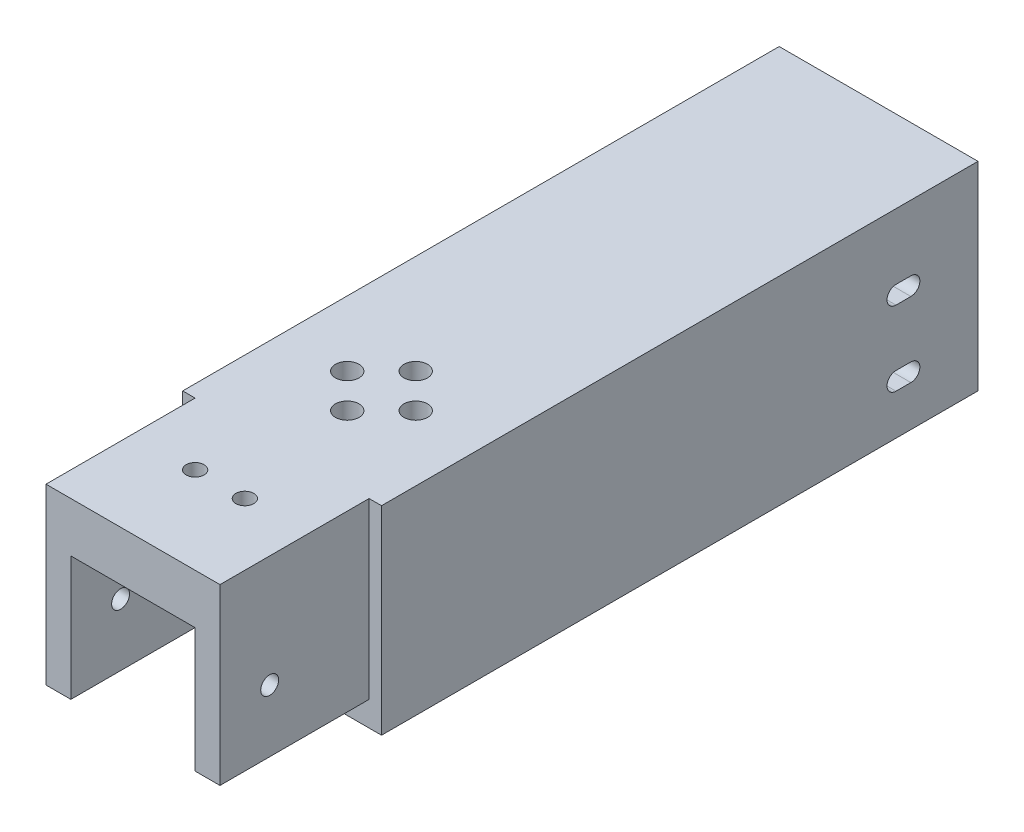
SolidWorks part; units mm, degrees
ref_plane "Front Plane" through (0, 0, 0) normal (0, 0, 1) x (1, 0, 0)
ref_plane "Top Plane" through (0, 0, 0) normal (0, 1, 0) x (1, 0, 0)
ref_plane "Right Plane" through (0, 0, 0) normal (1, 0, 0) x (0, 0, -1)
sketch "Sketch1" plane through (0, 0, 0) normal (0, 1, 0) x (1, 0, 0)
  line L9 (-20, -20) -> (20, -20)
  line L10 (-20, -20) -> (-20, 20)
  line L11 (-20, 20) -> (20, 20)
  line L12 (20, -20) -> (20, 20)
  line L13 (-20, -20) -> (20, 20) construction
  line L14 (-20, 20) -> (20, -20) construction
  circle A0 centre (6.88, 0) radius 2.375
  circle A1 centre (-0.0097, -6.8897) radius 2.375
  circle A2 centre (-6.8993, 0) radius 2.375
  circle A3 centre (-0.0097, 6.8897) radius 2.375
  point P2 (0, 0)
  point P12 (-0.0097, 0)
  dimension "D2" = 4.75
  dimension "D3" = 4
  dimension "D4" = 40
  dimension "D1" = 6.88
  dimension "D5" = 40
extrude "Boss-Extrude1" add sketch "Sketch1" along normal blind 40
sketch "Sketch3" plane through (0, 0, 20) normal (0, 0, 1) x (1, 0, 0)
  line L0 (-20, 0) -> (35335.3391, 35355.3391) construction
  line L1 (-20, 40) -> (35335.3391, -35315.3391) construction
  line L2 (-20, 40) -> (-20, 0) construction
  line L5 (-20, 0) -> (20, 0) construction
  line L6 (20, 40) -> (20, 0) construction
  circle A2 centre (0, 13) radius 3
  circle A3 centre (-7, 20) radius 3
  circle A4 centre (7, 20) radius 3
  point P10 (0, 20)
  dimension "D2" = 6
  dimension "D3" = 6
  dimension "D1" = 6
  dimension "D4" = 13
  dimension "D5" = 13
  dimension "D6" = 13
sketch "Sketch4" plane through (-20, 0, 0) normal (-1, 0, 0) x (0, 0, 1)
  line L0 (-20, 35) -> (-20, 0)
  line L1 (-20, 40) -> (-20, 0) construction
  line L2 (-20, 0) -> (15, 0)
  arc A0 (-20, 35) -> (15, 0) centre (-20, 0) cw
extrude "Cut-Extrude1" cut sketch "Sketch4" along normal through all both and the other way through all
sketch "Sketch6" plane through (0, 0, 0) normal (0, -1, 0) x (1, 0, 0)
  line L0 (20, -20) -> (-20, -20) construction
  line L2 (-15, 15) -> (-15, -20)
  line L3 (-15, -20) -> (15, -20)
  line L4 (15, 15) -> (15, -20)
  line L5 (-11.25, 15) -> (15, -20) construction
  line L6 (-15, -20) -> (11.25, 15) construction
  line L7 (-20, 15) -> (-20, -20) construction
  line L8 (-15, 15) -> (15, 15)
  point P0 (0, 0)
  dimension "D1" = 5
extrude "Cut-Extrude2" cut sketch "Sketch6" against normal blind 35 and the other way through all
extrude "Cut-Extrude3" cut sketch "Sketch3" against normal through all
sketch "Sketch7" plane through (0, 0, 20) normal (0, 0, 1) x (1, 0, 0)
  line L1 (-12.5, 30) -> (12.5, 30) construction
  line L2 (-12.5, 30) -> (-12.5, 5) construction
  line L3 (-12.5, 5) -> (12.5, 5) construction
  line L4 (12.5, 30) -> (12.5, 5) construction
  line L5 (-12.5, 30) -> (12.5, 5) construction
  line L6 (-12.5, 5) -> (12.5, 30) construction
  line L7 (-17.5, 40) -> (17.5, 40)
  line L9 (-12.5, 30) -> (12.5, 30)
  line L12 (-17.5, 23.7908) -> (-17.5, 40)
  line L14 (-12.5, 30) -> (-12.5, 5)
  line L15 (-12.5, 5) -> (-17.5, 5)
  line L16 (-17.5, 23.7908) -> (-17.5, 5)
  line L17 (12.5, 5) -> (17.5, 5)
  line L18 (12.5, 5) -> (12.5, 30)
  line L21 (17.5, 40) -> (17.5, 5)
  line L22 (-20, 40) -> (20, 40) construction
  circle A0 centre (-7, 20) radius 3 construction
  point P0 (0, 17.5)
  dimension "D1" = 7
  dimension "D4" = 10
  dimension "D6" = 5
  dimension "D2" = 25
  dimension "D3" = 25
  dimension "D7" = 5
extrude "Boss-Extrude2" add sketch "Sketch7" along normal blind 30
sketch "Sketch8" plane through (0, 40, 0) normal (0, 1, 0) x (1, 0, 0)
  line L0 (0, -1000) -> (0, 49000) construction
  line L2 (17.5, -20) -> (20, -20) construction
  circle A0 centre (5, -32.5) radius 1.8
  circle A1 centre (-5, -32.5) radius 1.8
  dimension "D3" = 3.6
  dimension "D1" = 5
  dimension "D2" = 12.5
extrude "Cut-Extrude4" cut sketch "Sketch8" against normal through all
sketch "Sketch10" plane through (0, 0, -20) normal (0, 0, -1) x (-1, 0, 0)
  line L2 (-20, 40) -> (-20, 0)
  line L3 (-20, 0) -> (-15, 0)
  line L4 (-15, 35) -> (-15, 0)
  line L5 (15, 0) -> (20, 0)
  line L6 (15, 0) -> (15, 35)
  line L8 (20, 0) -> (20, 40)
  line L9 (15, 35) -> (-15, 35)
  line L10 (20, 35) -> (20, 40)
  line L11 (20, 40) -> (-20, 40)
  line L12 (-20, 35) -> (-20, 40)
  line M5 (-20, 40) -> (-20, 35)
  line M6 (-20, 35) -> (-15, 35)
  line M7 (-15, 35) -> (15, 35)
  line M8 (15, 35) -> (20, 35)
  line M9 (20, 35) -> (20, 40)
  line M10 (20, 40) -> (-20, 40)
  dimension "D1" = 5
sketch "Sketch11" plane through (0, 40, 0) normal (0, 1, 0) x (1, 0, 0)
  circle A0 centre (-0.0097, -6.8897) radius 2.375 construction
  circle A1 centre (6.88, 0) radius 2.375 construction
  circle A2 centre (-0.0097, 6.8897) radius 2.375 construction
  circle A3 centre (-6.8993, 0) radius 2.375 construction
  circle A4 centre (-0.0097, -6.8897) radius 2.375
  circle A5 centre (6.88, 0) radius 2.375
  circle A6 centre (-0.0097, 6.8897) radius 2.375
  circle A7 centre (-6.8993, 0) radius 2.375
extrude "Boss-Extrude4" add sketch "Sketch10" along normal blind 80 and the other way up to surface (40 mm away) contours M10 M5 M6 M7 M8 M9 | L5 L8 L6 M8 | L4 L2 L3 M6 region at (0, 37.5, -20) region at (17.5, 17.5, -20) region at (-17.5, 17.5, -20) other way up to face at (10, 20, 20)
extrude "Cut-Extrude5" cut sketch "Sketch11" against normal blind 70
sketch "Sketch13" plane through (-20, 0, 0) normal (-1, 0, 0) x (0, 0, 1)
  line L0 (-86.5, 25) -> (-83.5, 25) construction
  line L1 (-86.5, 26.8) -> (-83.5, 26.8)
  line L2 (-86.5, 23.2) -> (-83.5, 23.2)
  line L3 (-100, 40) -> (20, 40) construction
  line L4 (-100, 0) -> (-100, 40) construction
  line L5 (-1100, 17.5) -> (48900, 17.5) construction
  line L7 (-100, 0) -> (20, 0) construction
  line L8 (-86.5, 10) -> (-83.5, 10) construction
  line L9 (-86.5, 8.2) -> (-83.5, 8.2)
  line L10 (-86.5, 11.8) -> (-83.5, 11.8)
  arc A0 (-86.5, 26.8) -> (-86.5, 23.2) centre (-86.5, 25) ccw
  arc A1 (-83.5, 23.2) -> (-83.5, 26.8) centre (-83.5, 25) ccw
  arc A2 (-86.5, 8.2) -> (-86.5, 11.8) centre (-86.5, 10) cw
  arc A3 (-83.5, 11.8) -> (-83.5, 8.2) centre (-83.5, 10) cw
  point P2 (-85, 25)
  point P17 (-85, 10)
  dimension "D1" = 1.8
  dimension "D2" = 3
  dimension "D3" = 15
  dimension "D4" = 15
  dimension "D5" = 17.5
extrude "Cut-Extrude6" cut sketch "Sketch13" against normal through all both and the other way through all
sketch "Sketch14" plane through (0, 35, 0) normal (0, -1, 0) x (1, 0, 0)
  line L0 (15, -100) -> (15, 15) construction
  line L1 (-15, -100) -> (15, -100)
  line L2 (-15, -100) -> (-15, -97)
  line L3 (-15, -97) -> (15, -97)
  line L4 (15, -100) -> (15, -97)
  line L5 (-15, 15) -> (-15, -100) construction
  line L6 (-15, -47) -> (15, -47)
  line L7 (-15, -47) -> (-15, -44)
  line L8 (-15, -44) -> (15, -44)
  line L9 (15, -47) -> (15, -44)
  line L10 (-15, -22) -> (-15, -19)
  line L11 (-15, -22) -> (15, -22)
  line L12 (15, -22) -> (15, -19)
  line L13 (-15, -19) -> (15, -19)
  dimension "D1" = 3
  dimension "D2" = 3
  dimension "D3" = 50
  dimension "D4" = 30
  dimension "D5" = 2
extrude "Boss-Extrude10" add sketch "Sketch14" along normal up to surface (35 mm away) up to face at (0, 0, -41.25)
sketch "Sketch16" plane through (0, 35, 0) normal (0, -1, 0) x (1, 0, 0)
  line L1 (15, 15) -> (-15, 15)
  line L2 (15, 15) -> (15, -19)
  line L3 (15, -19) -> (-15, -19)
  line L4 (-15, 15) -> (-15, -19)
extrude "Cut-Extrude7" cut sketch "Sketch16" against normal blind 1.5 and the other way through all
sketch "Sketch17" plane through (0, 0, -47) normal (0, 0, -1) x (-1, 0, 0)
  line L0 (0, -8.5238) -> (0, 5.4762) construction
  line L1 (-15, -8.5238) -> (-15, 5.4762)
  line L2 (15, -8.5238) -> (15, 5.4762)
  line L3 (-15, 0) -> (-15, 35) construction
  arc A0 (-15, -8.5238) -> (15, -8.5238) centre (0, -8.5238) ccw
  arc A1 (15, 5.4762) -> (-15, 5.4762) centre (0, 5.4762) ccw
  point P2 (0, -1.5238)
  dimension "D1" = 7
extrude "Cut-Extrude8" cut sketch "Sketch17" against normal blind 32.5
sketch "Sketch19" plane through (-17.5, 0, 0) normal (-1, 0, 0) x (0, 0, 1)
  line L0 (50, 5) -> (20, 5) construction
  line L1 (50, 40) -> (50, 5) construction
  circle A0 centre (40, 17.5) radius 1.8
  dimension "D1" = 3.6
  dimension "D3" = 10
  dimension "D2" = 12.5
extrude "Cut-Extrude9" cut sketch "Sketch19" against normal through all both and the other way through all
extrude "Boss-Extrude11" add sketch "Sketch3<2>" against normal up to surface (5 mm away) up to face at (-3, 13, 15)
sketch "Sketch3<2>" plane through (0, 0, 20) normal (0, 0, 1) x (1, 0, 0) same geometry as "Sketch3"
